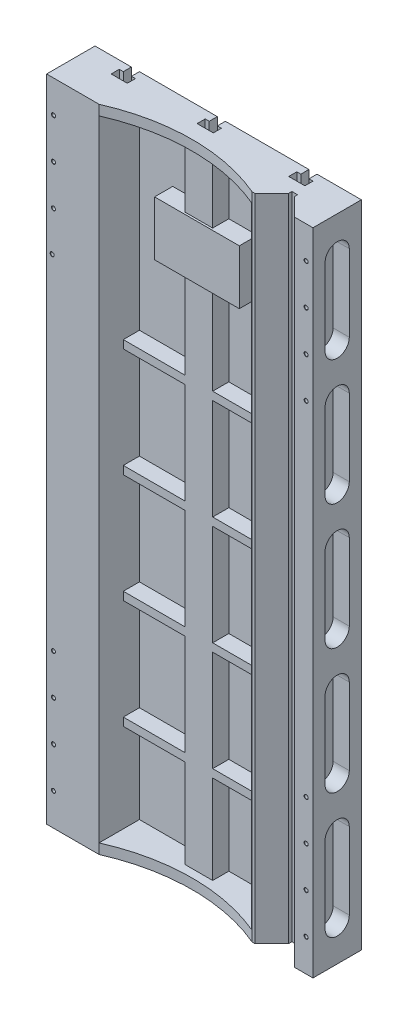
SolidWorks part; units mm, degrees
ref_plane "前视基准面" through (0, 0, 0) normal (0, 0, 1) x (1, 0, 0)
ref_plane "上视基准面" through (0, 0, 0) normal (0, 1, 0) x (1, 0, 0)
ref_plane "右视基准面" through (0, 0, 0) normal (1, 0, 0) x (0, 0, -1)
sketch "草图1" plane through (0, 0, 0) normal (0, 0, 1) x (1, 0, 0)
  line L1 (-330, 805) -> (330, 805)
  line L2 (-330, 805) -> (-330, -805)
  line L3 (-330, -805) -> (330, -805)
  line L4 (330, 805) -> (330, -805)
  line L5 (-330, 805) -> (330, -805) construction
  line L6 (-330, -805) -> (330, 805) construction
  point P0 (0, 0)
  dimension "D1" = 660
  dimension "D2" = 1610
extrude "凸台-拉伸2" add sketch "草图1" against normal blind 120
sketch "草图2" plane through (0, 0, 0) normal (0, 0, 1) x (1, 0, 0)
  line L0 (-330, -805) -> (-295, -805)
  line L1 (-330, -805) -> (330, -805) construction
  line L2 (-295, -805) -> (-295, 805)
  line L3 (330, 805) -> (-330, 805) construction
  line L4 (-330, 805) -> (-330, -805) construction
  line L5 (-295, 805) -> (-200, 805)
  line L6 (-200, 805) -> (-200, -805)
  line L7 (-200, -805) -> (175, -805)
  line L8 (175, -805) -> (175, 805)
  line L9 (175, 805) -> (200, 805)
  line L10 (200, 805) -> (200, -805)
  line L11 (200, -805) -> (295, -805)
  line L12 (295, -805) -> (295, 805)
  line L13 (-200, -780) -> (175, -780)
  line L14 (-200, 780) -> (175, 780)
  line L15 (-200, 805) -> (175, 805)
  line L20 (-200, 805) -> (175, 805)
  line L21 (-200, 780) -> (175, 780)
  line L23 (-200, -780) -> (175, -780)
  line L24 (-200, -780) -> (-200, 780)
  line L25 (-200, 780) -> (175, 780)
  line L26 (175, -780) -> (175, 780)
  point P22 (-314.4761, -805)
  point P23 (-314.4761, -725)
  point P24 (-314.4761, -805)
  point P25 (-314.4761, -725)
  point P26 (-312.5, -754.6187)
  point P27 (-314.4761, -727.1898)
  point P28 (-314.4761, -625)
  point P29 (-314.4761, -525)
  point P30 (-314.4761, -425)
  point P38 (-314.4761, -625)
  dimension "D1" = 35
  dimension "D2" = 95
  dimension "D3" = 375
  dimension "D4" = 25
  dimension "D5" = 95
  dimension "D6" = 25
  dimension "D7" = 25
  dimension "D8" = 80
  dimension "D9" = 100
  dimension "D10" = 100
  dimension "D11" = 100
  dimension "D12" = 17.5
sketch "草图5" plane through (0, 0, 0) normal (0, 0, 1) x (1, 0, 0)
  line L0 (-200, 805) -> (175, 805)
  line L1 (175, 805) -> (175, -805)
  line L2 (175, -805) -> (-200, -805)
  line L3 (-200, -805) -> (-200, 805)
sketch "草图7" plane through (0, 0, 0) normal (0, 0, 1) x (1, 0, 0)
  line L1 (175, 805) -> (-200, 805)
  line L2 (175, 805) -> (175, -805)
  line L3 (175, -805) -> (-200, -805)
  line L4 (-200, 805) -> (-200, -805)
sketch "草图9" plane through (0, 0, 0) normal (0, 0, 1) x (1, 0, 0)
  line L0 (175, 780) -> (175, -780)
  line L1 (175, -780) -> (-200, -780)
  line L2 (-200, -780) -> (-200, 780)
  line L3 (-200, 780) -> (175, 780)
extrude "切除-拉伸1" cut sketch "草图9" against normal blind 100
sketch "草图11" plane through (0, 0, -100) normal (0, 0, 1) x (1, 0, 0)
  line L0 (-200, -780) -> (-46.5, -780)
  line L1 (-200, -780) -> (175, -780) construction
  line L2 (-46.5, -780) -> (-46.5, 780)
  line L3 (-200, 780) -> (175, 780) construction
  line L4 (-46.5, 780) -> (21.5, 780)
  line L5 (21.5, 780) -> (21.5, -780)
  line L6 (21.5, -780) -> (175, -780)
  line L7 (-46.5, -780) -> (21.5, -780)
  line L8 (-46.5, -780) -> (21.5, -780)
  line L9 (21.5, 780) -> (-46.5, 780)
  dimension "D1" = 153.5
  dimension "D2" = 68
sketch "草图12" plane through (0, 0, -100) normal (0, 0, 1) x (1, 0, 0)
  line L1 (21.5, 780) -> (-46.5, 780)
  line L2 (21.5, 780) -> (21.5, -780)
  line L3 (21.5, -780) -> (-46.5, -780)
  line L4 (-46.5, 780) -> (-46.5, -780)
sketch "草图14" plane through (0, 0, -100) normal (0, 0, 1) x (1, 0, 0)
  line L0 (-200, -780) -> (-200, -560)
  line L1 (-200, 805) -> (-200, -805) construction
  dimension "D1" = 220
sketch "草图15" plane through (0, 0, -100) normal (0, 0, 1) x (1, 0, 0)
  line L0 (-200, -780) -> (-200, -560)
  line L1 (-200, -560) -> (175, -560)
  line L2 (175, -780) -> (175, 780) construction
  line L3 (175, -560) -> (175, -540)
  line L4 (175, -540) -> (-200, -540)
  line L5 (-200, 780) -> (-200, -780) construction
  line L6 (-200, -540) -> (-200, -560)
  line L7 (-200, -540) -> (-200, -290)
  line L8 (-200, -290) -> (175, -290)
  line L9 (175, -290) -> (175, -270)
  line L10 (175, -270) -> (-200, -270)
  line L11 (-200, -270) -> (-200, -290)
  dimension "D1" = 220
  dimension "D2" = 20
  dimension "D3" = 250
  dimension "D4" = 20
sketch "草图16" plane through (0, 0, -100) normal (0, 0, 1) x (1, 0, 0)
  line L1 (-200, -540) -> (175, -540)
  line L2 (-200, -540) -> (-200, -560)
  line L3 (-200, -560) -> (175, -560)
  line L4 (175, -540) -> (175, -560)
extrude "凸台-拉伸4" add sketch "草图16" along normal blind 40
pattern_linear "阵列(线性)1" count 4 spacing 270 along (0, 1, 0) of "凸台-拉伸4"
extrude "凸台-拉伸5" add sketch "草图12" along normal blind 40
sketch "草图37" plane through (330, 0, 0) normal (1, 0, 0) x (0, 0, -1)
  line L0 (60, -525) -> (60, -715) construction
  line L1 (90, -525) -> (90, -715)
  line L2 (30, -525) -> (30, -715)
  line L3 (0, -805) -> (0, 805) construction
  line L4 (120, -805) -> (0, -805) construction
  line L5 (120, -805) -> (120, 805) construction
  arc A0 (90, -525) -> (30, -525) centre (60, -525) ccw
  arc A1 (30, -715) -> (90, -715) centre (60, -715) ccw
  point P2 (60, -620)
  dimension "D1" = 90
  dimension "D2" = 190
  dimension "D3" = 30
  dimension "D4" = 30
extrude "切除-拉伸2" cut sketch "草图37" against normal blind 40
sketch "草图39" plane through (0, -805, 0) normal (0, -1, 0) x (1, 0, 0)
  line L2 (200, 0) -> (295, 0) construction
  line L3 (295, 0) -> (251.25, -43.75)
  line L5 (237.25, -43.75) -> (193.5, 0)
  line L6 (193.5, 0) -> (295, 0)
  line L7 (244.25, 56.6352) -> (244.25, -43.75) construction
  line L8 (251.25, -43.75) -> (251.25, -51.75)
  line L10 (330, -120) -> (330, 0) construction
  line L11 (237.25, -43.75) -> (237.25, -51.75)
  line L12 (237.25, -51.75) -> (251.25, -51.75)
  line M7 (330, 0) -> (-330, 0)
  dimension "D1" = 101.5
  dimension "D2" = 45
  dimension "D3" = 8
  dimension "D4" = 45
  dimension "D5" = 35
  dimension "D6" = 8
extrude "切除-拉伸3" cut sketch "草图39" against normal through all contours L5 L3 M7 region at (244.25, -805, -17.6838)
pattern_linear "阵列(线性)5" count 5 spacing 310 along (0, 1, 0) of "切除-拉伸2"
pattern_linear "阵列(线性)6" count 2 spacing 620 along (-1, 0, 0) of "切除-拉伸2", "阵列(线性)5"
sketch "草图41" plane through (0, -805, 0) normal (0, -1, 0) x (1, 0, 0)
  line L0 (330, -120) -> (220, -120)
  line L1 (-330, -120) -> (330, -120) construction
  line L2 (220, -120) -> (220, -100)
  line L3 (220, -100) -> (230, -100)
  line L4 (230, -100) -> (230, -80)
  line L5 (230, -80) -> (190, -80)
  line L6 (210, -80) -> (210, -120) construction
  line L7 (200, -120) -> (200, -100)
  line L8 (200, -100) -> (190, -100)
  line L9 (190, -100) -> (190, -80)
  line M11 (-330, -120) -> (330, -120)
  dimension "D1" = 110
  dimension "D2" = 20
  dimension "D3" = 10
  dimension "D4" = 20
  dimension "D5" = 20
extrude "切除-拉伸5" cut sketch "草图41" against normal through all contours L6 L5 L9 L8 L7 M11 | L5 L6 L2 L3 L4 M11 region at (218.3333, -805, -96.6667) region at (201.6667, -805, -96.6667)
pattern_linear "阵列(线性)7" count 2 spacing 440 along (-1, 0, 0) of "切除-拉伸5"
sketch "草图45" plane through (0, -805, 0) normal (0, -1, 0) x (1, 0, 0)
  line L0 (-330, 0) -> (193.5, 0) construction
  line L1 (175, 0) -> (-200, 0) construction
  line L2 (-200, 0) -> (175, 0)
  arc A0 (-200, 0) -> (175, 0) centre (-12.5, 1107.311) ccw
  line M25 (193.5, 0) -> (-330, 0)
extrude "切除-拉伸6" cut sketch "草图45" against normal through all contours A0 M25 region at (-12.5, -805, -6.3088)
sketch "草图46" plane through (0, 0, -100) normal (0, 0, 1) x (1, 0, 0)
  line L0 (-46.5, 780) -> (-46.5, 270) construction
  line L1 (-117.5, 620) -> (-46.5, 620)
  line L2 (-117.5, 620) -> (-117.5, 485)
  line L3 (-117.5, 485) -> (-46.5, 485)
  line L4 (-46.5, 620) -> (-46.5, 485)
  line L5 (21.5, 270) -> (21.5, 780) construction
  line L6 (21.5, 620) -> (92.5, 620)
  line L7 (21.5, 620) -> (21.5, 485)
  line L8 (21.5, 485) -> (92.5, 485)
  line L9 (92.5, 620) -> (92.5, 485)
  line L10 (-200, 780) -> (175, 780) construction
  line L11 (175, 780) -> (21.5, 780) construction
  dimension "D1" = 71
  dimension "D2" = 135
  dimension "D3" = 135
  dimension "D4" = 71
  dimension "D5" = 160
  dimension "D6" = 160
extrude "凸台-拉伸7" add sketch "草图46" along normal blind 40
pattern_linear "阵列(线性)9" count 2 spacing 213 along (1, 0, 0) of "阵列(线性)7"
sketch "草图49" plane through (0, 0, -60) normal (0, 0, 1) x (1, 0, 0)
  line L0 (21.5, 485) -> (92.5, 485) construction
  line L1 (92.5, 485) -> (-117.5, 485)
  line L2 (92.5, 485) -> (92.5, 620)
  line L3 (92.5, 620) -> (-117.5, 620)
  line L4 (-117.5, 485) -> (-117.5, 620)
  line L5 (-117.5, 620) -> (-117.5, 485) construction
  dimension "D1" = 210
  dimension "D2" = 135
  dimension "D3" = 0
extrude "凸台-拉伸8" add sketch "草图49" along normal blind 5
sketch "草图50" [suppressed] plane through (0, 0, 0) normal (0, 0, 1) x (1, 0, 0)
  line L0 (-313, 805) -> (-313, -805) construction
  line L1 (-200, 805) -> (-330, 805) construction
  line L2 (-330, -805) -> (-200, -805) construction
  line L3 (-330, 805) -> (-330, -805) construction
  circle A0 centre (-313, -725) radius 5
  point P6 (-313, -725)
  dimension "D1" = 17
  dimension "D2" = 80
sketch "草图53" plane through (0, 0, 0) normal (0, 0, 1) x (1, 0, 0)
  line L0 (-330, -805) -> (-200, -805) construction
  line L1 (-330, 805) -> (-330, -805) construction
  line L2 (-200, 805) -> (-330, 805) construction
  point P0 (-313, -725)
  point P2 (-313, -625)
  point P4 (-313, -525)
  point P6 (-313, -425)
  point P36 (-313, 725)
  point P46 (-313, 625)
  point P48 (-313, 525)
  point P50 (-316.2819, 425)
  dimension "D1" = 80
  dimension "D2" = 17
  dimension "D3" = 17
  dimension "D4" = 100
  dimension "D5" = 17
  dimension "D6" = 17
  dimension "D7" = 100
  dimension "D8" = 90
  dimension "D9" = 17
  dimension "D10" = 80
  dimension "D11" = 100
  dimension "D12" = 100
  dimension "D13" = 100
hole_wizard "M10x1.25 螺纹孔3" positions "草图53" profile "草图54" tap size "M10x1.25" standard "GB"
sketch "草图54" plane through (-313, -725, 0) normal (1, 0, 0) x (0, -1, 0)
  line L0 (0, 0) -> (0, 52)
  line L1 (0, 52) -> (4.4, 49.3562)
  line L2 (4.4, 49.3562) -> (4.4, 0.625)
  line L3 (4.4, 0.625) -> (5.025, 0)
  line L5 (5.025, 0) -> (0, 0)
  line L6 (-4.4, 0.625) -> (-5.025, 0) construction
  line L10 (0, 52) -> (-4.4, 49.3562) construction
  line L11 (0, -6.35) -> (0, 107.95) construction
  dimension "螺纹孔钻头直径" = 8.8
  dimension "螺纹孔钻头深度" = 52
  dimension "近端锥形沉头孔直径" = 10.05
  dimension "近端锥形沉头孔角度" = 90
  dimension "导头角度" = 118
cosmetic thread "孔螺蚊线21" parameters "D1"=20, "D2"=10
cosmetic thread "孔螺蚊线22" parameters "D1"=20, "D2"=10
cosmetic thread "孔螺蚊线23" parameters "D1"=20, "D2"=10
cosmetic thread "孔螺蚊线24" parameters "D1"=20, "D2"=10
cosmetic thread "孔螺蚊线25" parameters "D1"=20, "D2"=10
cosmetic thread "孔螺蚊线26" parameters "D1"=20, "D2"=10
cosmetic thread "孔螺蚊线27" parameters "D1"=20, "D2"=10
cosmetic thread "孔螺蚊线28" parameters "D1"=20, "D2"=10
sketch "草图56" plane through (0, 0, 0) normal (0, 0, 1) x (1, 0, 0)
  line L0 (295, -805) -> (330, -805) construction
  line L1 (330, -805) -> (330, 805) construction
  point P0 (313, -725)
  dimension "D1" = 80
  dimension "D2" = 17
hole_wizard "M10x1.25 螺纹孔1" positions "草图56" profile "草图57" tap size "M10x1.25" standard "GB"
sketch "草图57" plane through (313, -725, 0) normal (1, 0, 0) x (0, -1, 0)
  line L0 (0, 0) -> (0, 52)
  line L1 (0, 52) -> (4.4, 49.3562)
  line L2 (4.4, 49.3562) -> (4.4, 0.625)
  line L3 (4.4, 0.625) -> (5.025, 0)
  line L5 (5.025, 0) -> (0, 0)
  line L6 (-4.4, 0.625) -> (-5.025, 0) construction
  line L10 (0, 52) -> (-4.4, 49.3562) construction
  line L11 (0, -6.35) -> (0, 107.95) construction
  dimension "螺纹孔钻头直径" = 8.8
  dimension "螺纹孔钻头深度" = 52
  dimension "近端锥形沉头孔直径" = 10.05
  dimension "近端锥形沉头孔角度" = 90
  dimension "导头角度" = 118
cosmetic thread "孔螺蚊线13" parameters "D1"=20, "D2"=10
hole_wizard "M10x1.25 螺纹孔2" positions "3D草图2" profile "草图58" tap size "M10x1.25" standard "GB"
sketch3d "3D草图2"
  line L0 (330, 805, 0) -> (295, 805, 0) construction
  line L1 (330, -805, 0) -> (330, 805, 0) construction
  point P0 (313, 725, 0)
  dimension "D1" = 80
  dimension "D2" = 17
sketch "草图58" plane through (313, 725, 0) normal (1, 0, 0) x (0, -1, 0)
  line L0 (0, 0) -> (0, 52)
  line L1 (0, 52) -> (4.4, 49.3562)
  line L2 (4.4, 49.3562) -> (4.4, 0.625)
  line L3 (4.4, 0.625) -> (5.025, 0)
  line L5 (5.025, 0) -> (0, 0)
  line L6 (-4.4, 0.625) -> (-5.025, 0) construction
  line L10 (0, 52) -> (-4.4, 49.3562) construction
  line L11 (0, -6.35) -> (0, 107.95) construction
  dimension "螺纹孔钻头直径" = 8.8
  dimension "螺纹孔钻头深度" = 52
  dimension "近端锥形沉头孔直径" = 10.05
  dimension "近端锥形沉头孔角度" = 90
  dimension "导头角度" = 118
cosmetic thread "孔螺蚊线14" parameters "D1"=20, "D2"=10
pattern_linear "阵列(线性)11" count 4 spacing 100 along (0, -1, 0) of "M10x1.25 螺纹孔2"
cosmetic thread "孔螺蚊线15" parameters "D1"=20, "D2"=10
cosmetic thread "孔螺蚊线16" parameters "D1"=20, "D2"=10
cosmetic thread "孔螺蚊线17" parameters "D1"=20, "D2"=10
pattern_linear "阵列(线性)12" count 4 spacing 100 along (0, 1, 0) of "M10x1.25 螺纹孔1"
cosmetic thread "孔螺蚊线18" parameters "D1"=20, "D2"=10
cosmetic thread "孔螺蚊线19" parameters "D1"=20, "D2"=10
cosmetic thread "孔螺蚊线20" parameters "D1"=20, "D2"=10
sketch "草图60" plane through (0, -805, 0) normal (0, -1, 0) x (1, 0, 0)
  line L1 (175, 0) -> (193.5, 0) construction
  line L2 (175, 0) -> (181.5, 0)
  arc A1 (-200, 0) -> (181.5, 0) centre (-9.25, 434.8195) ccw
  arc A2 (-200, 0) -> (175, 0) centre (-12.5, 1107.311) ccw construction
  arc A3 (-200, 0) -> (175, 0) centre (-12.5, 1107.311) ccw
  point P12 (-9.25, -40)
  point P16 (-104.625, -20)
extrude "切除-拉伸7" cut sketch "草图60" against normal up to surface (1610 mm away) up to face at (31.7917, 805, -79.0767)
sketch "草图61" plane through (0, -805, 0) normal (0, -1, 0) x (1, 0, 0)
  line L0 (295, 0) -> (251.25, -43.75)
  line L1 (251.25, -43.75) -> (251.25, -51.75)
  line L2 (251.25, -51.75) -> (237.25, -51.75)
  line L3 (237.25, -51.75) -> (237.25, -43.75)
  line L4 (237.25, -43.75) -> (237.25, -51.75) construction
  line L5 (237.25, -43.75) -> (193.5, 0)
  line L6 (193.5, 0) -> (295, 0)
  line L7 (182.38, 0) -> (283.88, 0)
  line L8 (283.88, 0) -> (240.13, -43.75)
  line L9 (240.13, -43.75) -> (240.13, -51.75)
  line L10 (240.13, -51.75) -> (226.13, -51.75)
  line L11 (226.13, -51.75) -> (226.13, -43.75)
  line L12 (226.13, -43.75) -> (182.38, 0)
  line M43 (295, 0) -> (251.25, -43.75)
  line M44 (251.25, -43.75) -> (251.25, -51.75)
  line M45 (251.25, -51.75) -> (237.25, -51.75)
  line M46 (237.25, -51.75) -> (237.25, -43.75)
  line M47 (237.25, -43.75) -> (193.5, 0)
  line M48 (193.5, 0) -> (181.5, 0)
  dimension "D1" = 2
extrude "凸台-拉伸9" add sketch "草图61" against normal up to surface (1610 mm away) contours L8 L9 L6 M45 M44 M43 | L9 L8 L6 L2 M47 M46 region at (264.1834, -805, -25.875) region at (238.69, -805, -15.3991) up to face at (31.9722, 805, -79.75)
extrude "切除-拉伸8" cut sketch "草图61<3>" against normal up to surface (1610 mm away) contours L12 L11 L10 M46 M47 M48 | L9 L8 L6 L2 M47 M46 region at (238.69, -805, -15.3991) region at (213.1966, -805, -25.875) up to face at (-10.4833, 805, -89.3333)
sketch "草图61<3>" plane through (0, -805, 0) normal (0, -1, 0) x (1, 0, 0) same geometry as "草图61"
sketch "草图63" plane through (0, -805, 0) normal (0, -1, 0) x (1, 0, 0)
  line L0 (226.13, -43.75) -> (182.38, 0) construction
  line L1 (184.1542, -1.7742) -> (182.38, 0)
  line L2 (182.38, 0) -> (181.5, 0)
  line L3 (184.1542, -1.7742) -> (177.4035, -1.7742)
  arc A0 (-200, 0) -> (181.5, 0) centre (-9.25, 434.8195) ccw construction
  arc A1 (177.4035, -1.7742) -> (181.5, 0) centre (-9.25, 434.8195) ccw
extrude "切除-拉伸10" cut sketch "草图63" against normal up to surface (1610 mm away) up to face at (30.1189, 805, -79.75)
